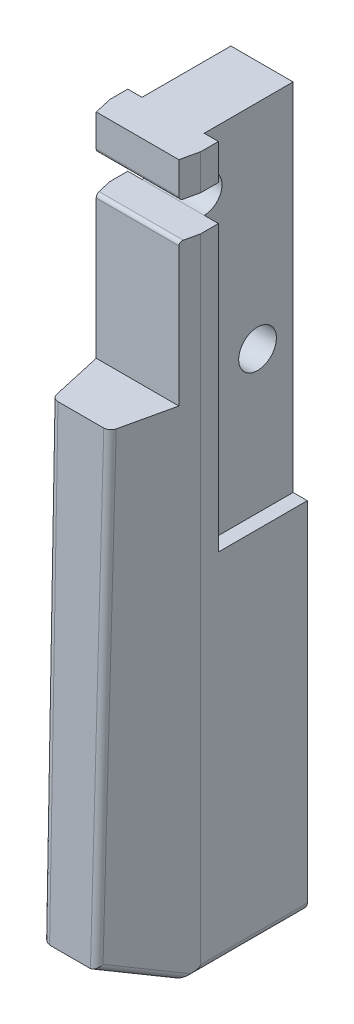
SolidWorks part; units mm, degrees
ref_plane "Front Plane" through (0, 0, 0) normal (1, 0, 0) x (0, 1, 0)
ref_plane "Top Plane" through (0, 0, 0) normal (0, 0, 1) x (0, 1, 0)
ref_plane "Right Plane" through (0, 0, 0) normal (0, 1, 0) x (-1, 0, 0)
sketch "Sketch1" plane through (0, 0, 0) normal (0, 0, 1) x (0, 1, 0)
  line L1 (0, 0) -> (100, 0)
  line L2 (0, 0) -> (0, 11.75)
  line L3 (0, 11.75) -> (100, 11.75)
  line L4 (100, 0) -> (100, 11.75)
  dimension "D1" = 100
  dimension "D2" = 11.75
extrude "Boss-Extrude1" add sketch "Sketch1" along normal blind 17.5
sketch "Sketch5" plane through (0, 0, 0) normal (1, 0, 0) x (0, 1, 0)
  line L1 (100, 17.5) -> (70, 17.5)
  line L2 (100, 17.5) -> (100, 5)
  line L3 (100, 5) -> (70, 5)
  line L4 (70, 17.5) -> (70, 5)
  circle A0 centre (70, 5) radius 2.65
  dimension "D1" = 30
extrude "Cut-Extrude2" cut sketch "Sketch5" against normal through all contours A0
sketch "Sketch4" plane through (0, 0, 0) normal (1, 0, 0) x (0, 1, 0)
  line L0 (100, 17.5) -> (100, 12.5)
  line L1 (100, 17.5) -> (100, 0) construction
  line L3 (100, 12.5) -> (50, 12.5)
  line L4 (100, 12.5) -> (100, 0)
  line L5 (100, 0) -> (50, 0)
  line L6 (50, 12.5) -> (50, 0)
  line M6 (0, 0) -> (100, 0)
  line M7 (100, 0) -> (100, 17.5)
  circle M10 centre (70, 5) radius 2.65
  dimension "D1" = 50
  dimension "D2" = 12.5
extrude "Cut-Extrude3" cut sketch "Sketch4" against normal blind 1.5 contours L3 L6 M6 M7 M10 region at (0, 75.183, 6.2957)
ref_plane "Plane1" through (-5.875, 0, 0) normal (1, 0, 0) x (0, 0, -1)
mirror "Mirror1" about plane through (-5.875, 0, 0) normal (1, 0, 0) of "Cut-Extrude3"
sketch "Sketch9" plane through (0, 0, 0) normal (1, 0, 0) x (0, 1, 0)
  line L1 (0, 17.5) -> (50, 17.5)
  line L2 (0, 17.5) -> (0, 0)
  line L3 (0, 0) -> (50, 0)
  line L4 (50, 12.5) -> (50, 0)
  line L5 (50, 17.5) -> (100, 17.5)
  line L7 (50, 12.5) -> (100, 12.5)
  line L8 (100, 17.5) -> (100, 12.5)
extrude "Boss-Extrude3" add sketch "Sketch9" along normal blind 0.5
mirror "Mirror4" about plane through (-5.875, 0, 0) normal (1, 0, 0) of "Boss-Extrude3"
sketch "Sketch6" plane through (0.5, 0, 0) normal (1, 0, 0) x (0, 1, 0)
  line L0 (0, 17.5) -> (4.75, 27)
  line L1 (4.75, 27) -> (90, 25)
  line L2 (90, 25) -> (100, 17.5)
  line L4 (70, 5) -> (70, 12.5) construction
  line L5 (70, 12.5) -> (70, 25.4692)
  line L6 (0, 17.5) -> (0, 0)
  line L7 (0, 0) -> (50, 0)
  line L8 (50, 0) -> (50, 12.5)
  line L9 (50, 12.5) -> (100, 12.5)
  line L12 (100, 12.5) -> (100, 17.5)
extrude "Boss-Extrude2" add sketch "Sketch6" against normal blind 12.75 contours L5 L1 L0 region at (0.5, 31.0716, 14.0937)
sketch "Sketch7" plane through (0, 100, 0) normal (0, 1, 0) x (-1, 0, 0)
  line L0 (-0.5, 15) -> (12.25, 15) construction
  line L1 (1.5, 0) -> (10.25, 0) construction
  line L2 (1.5, 0) -> (1.5, 17.5) construction
  line L3 (1.5, 17.5) -> (10.25, 17.5) construction
  line L4 (10.25, 0) -> (10.25, 17.5) construction
  line L7 (-0.5, 15) -> (2.202, 27)
  line L8 (12.25, 27) -> (-0.5, 27) construction
  line L9 (12.25, 12.5) -> (12.25, 17.5) construction
  line L10 (-0.5, 12.5) -> (-0.5, 17.5) construction
  line L11 (-0.5, 17.5) -> (-0.5, 15) construction
  line L12 (12.25, 17.5) -> (12.25, 15) construction
extrude "Cut-Extrude4" cut sketch "Sketch7" against normal through all and the other way through all
mirror "Mirror3" about plane through (-5.875, 0, 0) normal (1, 0, 0) of "Cut-Extrude4"
fillet "Fillet4" radius 1 5 edges at (-10.6175, 2.375, 22.25) (-5.875, 0, 17.5) (-1.1325, 2.375, 22.25) (-2.0297, 37.375, 26.2346) (-9.7203, 37.375, 26.2346)
fillet "Fillet3" radius 1 2 edges at (-12.25, 0, 7.5) (0.5, 0, 7.5)
sketch "Sketch11" plane through (0.5, 95.8808, 19.3496) normal (1, 0, 0) x (0, 0, 1)
  line L0 (-6.8496, 45.8808) -> (-6.8496, -4.1192) construction
  line L5 (-1.8496, -4.1192) -> (-6.8496, -4.1192)
  line L8 (-1.8496, -4.1192) -> (-1.8496, 3.3808)
  line L9 (-1.8496, 3.3808) -> (-6.8496, 3.3808)
  line L10 (-6.8496, -4.1192) -> (-6.8496, 3.3808)
  line L11 (-1.8496, 3.3808) -> (-6.8496, 3.3808) construction
  line L12 (-1.8496, 0.8808) -> (-6.8496, 0.8808)
  line L13 (-1.8496, 5.8808) -> (-6.8496, 5.8808)
  arc A4 (-1.8496, 0.8808) -> (-1.8496, 5.8808) centre (-1.8496, 3.3808) ccw
  arc A5 (-6.8496, 5.8808) -> (-6.8496, 0.8808) centre (-6.8496, 3.3808) ccw
  point P7 (-4.3496, 3.3808)
extrude "Cut-Extrude5" cut sketch "Sketch11" against normal up to next contours A4 L13 A5 L12
fillet "Fillet5" radius 0.5 2 edges at (-5.875, 95, 17.5) (-5.875, 90, 17.5)
sketch "Sketch12" plane through (0, 0, 0) normal (0, 0, -1) x (1, 0, 0)
  line L0 (-11.25, 0) -> (-0.5, 0) construction
  line L1 (0.5, 0) -> (-5.875, 0)
  line L2 (0.5, 0) -> (0.5, -13.5)
  line L3 (0.5, -13.5) -> (-5.875, -13.5)
  line L4 (-5.875, 0) -> (-5.875, -13.5)
  circle A0 centre (-5.875, -13.5) radius 3
  dimension "D4" = 6
  dimension "D1" = 13.5
  dimension "D2" = 6.375
extrude "Cut-Extrude6" cut sketch "Sketch12" against normal blind 5 contours A0
equation "\"whitekey_cutout_length\"= 101.5"
equation "\"mount_recess_length\"=50"
equation "\"mount_recess_height\"=12.5"
equation "\"mount_recess_depth\"=1.5"
equation "\"D1@Sketch4\"=\"mount_recess_length\""
equation "\"D2@Sketch4\"=\"mount_recess_height\""
equation "\"D1@Cut-Extrude3\"=\"mount_recess_depth\""
equation "\"D1@Sketch5\"=\"mount_recess_length\"-20"
equation "\"D1@Sketch1\"=\"whitekey_cutout_length\"-1.5"
